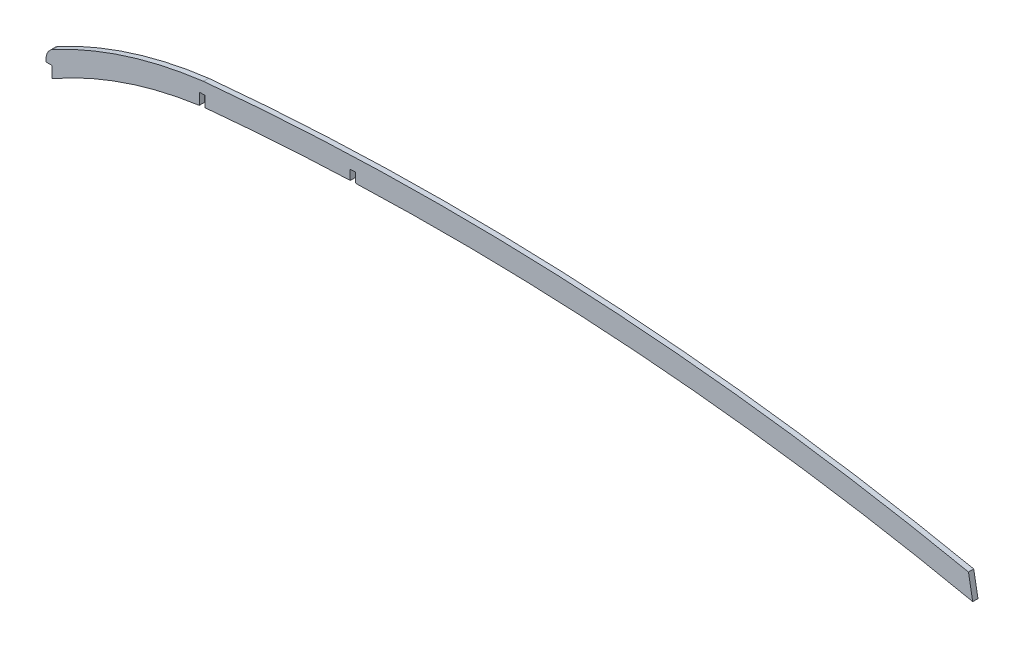
SolidWorks part; units mm, degrees
material "Balsa"
ref_plane "Front Plane" through (0, 0, 0) normal (0, 0, 1) x (1, 0, 0)
ref_plane "Top Plane" through (0, 0, 0) normal (0, 1, 0) x (1, 0, 0)
ref_plane "Right Plane" through (0, 0, 0) normal (1, 0, 0) x (0, 0, -1)
sketch "Sketch1" plane through (0, 0, 0) normal (0, 0, 1) x (1, 0, 0)
  line L0 (0, 101.6) -> (0, 100.0553)
  line L1 (0, -1.7463) -> (0, 1.7463) construction
  line L2 (0, 86.36) -> (8.1082, 86.36) construction
  line L3 (3.7499, 106.3536) -> (3.7499, -82.5359) construction
  line L4 (8.1082, 101.6) -> (0, 101.6) construction
  line L5 (92.329, 130.518) -> (92.329, 123.5672)
  line L6 (3.7499, 93.1973) -> (0, 91.0322) construction
  line L7 (0, 99.5163) -> (0, 88.039) construction
  line L8 (558.2295, 97.6273) -> (555.6382, 111.8229)
  line L9 (0, 91.0322) -> (0, 86.36) construction
  line L10 (3.7499, 93.1973) -> (3.7499, 100.0553)
  line L11 (3.7499, 100.0553) -> (0, 97.8902) construction
  line L12 (0, 97.8902) -> (0, 91.0322) construction
  line L13 (3.7499, 100.0553) -> (0, 100.0553)
  line L14 (0, 100.0553) -> (0, 97.8902) construction
  line L17 (92.3925, 137.6297) -> (92.3925, -54.5591) construction
  line L18 (95.631, 130.518) -> (95.631, 124.0109)
  line L19 (95.5675, -54.5591) -> (95.5675, 137.6297) construction
  line L20 (95.5675, 137.6297) -> (92.3925, 137.6297) construction
  line L21 (93.98, 137.6297) -> (93.98, 130.518) construction
  line L22 (92.329, 130.518) -> (95.631, 130.518)
  line L23 (92.329, 123.5672) -> (92.329, 122.506) construction
  line L24 (95.631, 124.0109) -> (95.631, 123.1918) construction
  line L25 (197.4984, -131.9724) -> (196.7865, -114.9693)
  line L26 (186.671, 126.627) -> (186.2782, 136.0069)
  line L27 (194.3262, -132.1052) -> (193.6143, -115.1021)
  line L28 (183.4987, 126.4942) -> (183.106, 135.8741)
  line L29 (193.6143, -115.1021) -> (196.7865, -114.9693)
  line L30 (186.671, 126.627) -> (183.4987, 126.4942)
  line L31 (194.3262, -132.1052) -> (197.4984, -131.9724)
  line L32 (183.106, 135.8741) -> (186.2782, 136.0069)
  line L33 (183.106, 135.8741) -> (186.2782, 136.0069) construction
  line L35 (186.671, 126.627) -> (183.4987, 126.4942) construction
  line L37 (183.4987, 126.4942) -> (183.106, 135.8741) construction
  line L39 (186.671, 126.627) -> (186.2782, 136.0069) construction
  line L41 (183.106, 135.8741) -> (186.671, 126.627) construction
  line L42 (184.8885, 131.2506) -> (184.9758, 129.1656) construction
  line L43 (183.294, 129.865) -> (183.0502, 135.6897)
  line L44 (186.5939, 129.9858) -> (186.3493, 135.8278)
  line L45 (183.0502, 135.6897) -> (186.3493, 135.8278)
  line L46 (183.2948, 129.8477) -> (183.294, 129.865) construction
  arc A0 (4.3005, 108.7585) -> (94.8544, 137.376) centre (127, -121.92) cw
  arc A1 (4.3005, 108.7585) -> (0, 101.6) centre (8.1082, 101.6) ccw
  arc A2 (3.7499, 93.1973) -> (0, 86.36) centre (8.1082, 86.36) ccw construction
  arc A3 (94.8544, 137.376) -> (555.6382, 111.8229) centre (240.8652, -1397) cw
  arc A4 (3.7499, 93.1973) -> (92.329, 123.5672) centre (127, -121.92) cw
  arc A5 (96.3112, 124.0967) -> (183.294, 129.865) centre (240.8652, -1397) cw
  arc A6 (10.5733, 96.9655) -> (96.3112, 124.0967) centre (127, -121.92) cw construction
  arc A7 (94.4927, 137.3434) -> (3.7499, 106.3536) centre (112.883, -64.8553) ccw construction
  arc A8 (96.3112, 124.0967) -> (552.9103, 98.7469) centre (240.8652, -1397) cw construction
  arc A9 (4.3005, 108.7585) -> (94.8544, 137.376) centre (127, -121.92) cw construction
  arc A10 (92.329, 123.5672) -> (95.631, 124.0109) centre (127, -121.92) cw construction
  arc A11 (94.8544, 137.376) -> (555.6382, 111.8229) centre (240.8652, -1397) cw construction
  arc A12 (95.631, 124.0109) -> (96.3112, 124.0967) centre (127, -121.92) cw
  arc A13 (556.7512, 105.7321) -> (99.1899, 122.2822) centre (270.5046, -1474.7614) ccw construction
  arc A14 (183.294, 129.865) -> (183.3575, 129.8673) centre (240.8652, -1397) cw construction
  arc A15 (184.9439, 129.9263) -> (185.3927, 129.9426) centre (240.8652, -1397) cw construction
  arc A16 (183.3575, 129.8673) -> (184.9439, 129.9263) centre (240.8652, -1397) cw construction
  arc A17 (185.3927, 129.9426) -> (186.5304, 129.9835) centre (240.8652, -1397) cw construction
  arc A18 (186.5939, 129.9858) -> (558.2295, 97.6273) centre (240.8652, -1397) cw
  arc A19 (186.5304, 129.9835) -> (186.5939, 129.9858) centre (240.8652, -1397) cw construction
  spline S0 degree 3 poles (981.3177, 1818.2675) (1139.722, 204.4849) (873.2182, 1.0169) (565.628, -88.9106) (559.2919, -90.7077) (-121.8164, -278.7114) (-929.5333, 36.0269) (-1233.6865, -867.5095) knots -11.664502 -11.664502 -11.664502 -11.664502 0.25 0.25 0.5 0.5 27.071012 27.071012 27.071012 27.071012 only from (590.8643, -81.3536) to (514.7143, -102.4537) construction
  spline S1 degree 3 poles (1062.5522, -1662.3274) (1783.386, 752.2598) (1192.007, 51.9761) (480.6823, -110.4688) (472.1454, -112.3347) (455.0337, -115.879) (446.4591, -117.5582) (433.5613, -119.8984) (429.2558, -120.648) (422.7903, -121.7356) (420.6337, -122.0915) (417.3979, -122.6188) (416.3191, -122.7935) (329.7173, -136.7537) (244.3749, -151.8452) (-150.7518, 1789.6158) knots -20.37019 -20.37019 -20.37019 -20.37019 0.25 0.25 0.5 0.5 0.75 0.75 0.875 0.875 0.9375 0.9375 0.96875 0.96875 3.445896 3.445896 3.445896 3.445896 only from (514.7143, -102.4537) to (412.003, -123.4859) construction
  spline S2 degree 3 poles (-1526.2092, 975.8893) (-966.7298, 244.4948) (-373.5074, -121.9571) (226.7788, -133.168) (266.5142, -132.8729) (279.7628, -132.6016) (299.6408, -131.9345) (306.2677, -131.6688) (319.5231, -131.0505) (326.1536, -130.6977) (943.6584, -93.7895) (1501.3881, 309.0053) (2017.121, 1001.2295) knots -5.168103 -5.168103 -5.168103 -5.168103 0.25 0.5 0.5 0.625 0.625 0.6875 0.6875 0.75 0.75 6.511417 6.511417 6.511417 6.511417 only from (94.4926, -125.8525) to (412.003, -123.4859) construction
  spline S3 degree 3 poles (82.8406, 1879.826) (-241.5287, 509.6599) (-195.4311, -0.6421) (32.0968, -110.0953) (39.5136, -113.1375) (50.922, -117.0433) (54.7721, -118.2354) (60.6197, -119.8556) (62.5829, -120.3681) (66.5243, -121.3341) (68.5001, -121.787) (343.1899, -180.4478) (711.1357, 326.3263) (1193.75, 1513.3939) knots -7.368418 -7.368418 -7.368418 -7.368418 0.25 0.25 0.5 0.5 0.625 0.625 0.6875 0.6875 0.75 0.75 9.354609 9.354609 9.354609 9.354609 only from (3.7499, -94.8626) to (94.4926, -125.8525) construction
  spline S6 degree 3 poles (590.8643, -81.3536) (584.5771, -83.3154) (578.2709, -85.2143) (565.628, -88.9106) (559.2919, -90.7077) (540.2459, -95.9648) (527.5015, -99.2922) (514.7143, -102.4537) knots 0 0 0 0 0.25 0.25 0.5 0.5 1 1 1 1 construction
  spline S7 degree 3 poles (514.7143, -102.4537) (506.2284, -104.5517) (497.724, -106.577) (480.6823, -110.4688) (472.1454, -112.3347) (455.0337, -115.879) (446.4591, -117.5582) (433.5613, -119.8984) (429.2558, -120.648) (422.7903, -121.7356) (420.6337, -122.0915) (417.3979, -122.6188) (416.3191, -122.7935) (414.1613, -123.1413) (413.0825, -123.3155) (412.003, -123.4859) knots 0 0 0 0 0.25 0.25 0.5 0.5 0.75 0.75 0.875 0.875 0.9375 0.9375 0.96875 0.96875 1 1 1 1 construction
  spline S8 degree 3 poles (94.4926, -125.8525) (120.9278, -128.4258) (173.8258, -132.179) (226.7788, -133.168) (266.5142, -132.8729) (279.7628, -132.6016) (299.6408, -131.9345) (306.2677, -131.6688) (319.5231, -131.0505) (326.1536, -130.6977) (359.2877, -128.7173) (385.6949, -126.4433) (412.003, -123.4859) knots 0 0 0 0 0.25 0.5 0.5 0.625 0.625 0.6875 0.6875 0.75 0.75 1 1 1 1 construction
  spline S9 degree 3 poles (3.7499, -94.8626) (10.597, -99.2271) (17.6385, -103.1401) (32.0968, -110.0953) (39.5136, -113.1375) (50.922, -117.0433) (54.7721, -118.2354) (60.6197, -119.8556) (62.5829, -120.3681) (66.5243, -121.3341) (68.5001, -121.787) (78.4043, -123.9021) (86.408, -125.1172) (94.4926, -125.8525) knots 0 0 0 0 0.25 0.25 0.5 0.5 0.625 0.625 0.6875 0.6875 0.75 0.75 1 1 1 1 construction
  spline S15 degree 3 poles (587.4426, -62.5747) (587.1827, -61.1511) (586.6535, -58.2526) (585.7873, -53.5174) (584.8512, -48.394) (583.8406, -42.8532) (582.7565, -36.9006) (581.5991, -30.5376) (580.1295, -22.4773) (578.3524, -12.6853) (576.2505, -1.1976) (574.1192, 10.4518) (571.9272, 22.5233) (569.819, 34.0829) (567.7342, 45.5019) (565.8232, 55.9911) (564.3841, 63.8754) (563.4512, 68.9947) (562.9209, 71.9076) (562.4102, 74.7138) (561.9192, 77.4122) (561.4478, 80.0018) (560.9959, 82.4822) (560.5637, 84.8528) (560.1512, 87.1138) (559.7582, 89.2651) (559.385, 91.3073) (559.0312, 93.2414) (558.6975, 95.0661) (558.3822, 96.7905) (558.1867, 97.8615) (558.0896, 98.3936) knots 0 0 0 0 0.031687 0.064515 0.098497 0.133644 0.169967 0.207478 0.246191 0.30842 0.370332 0.432609 0.495165 0.563925 0.620591 0.686243 0.746551 0.766006 0.785258 0.804303 0.823142 0.841774 0.860197 0.878411 0.896416 0.91421 0.931793 0.949164 0.966322 0.983268 1 1 1 1 construction
  point P53 (93.98, 130.518)
  dimension "D4" = 8.1082
  dimension "D2" = 127
  dimension "D8" = 1397
  dimension "D9" = 30
  dimension "D1" = 15.24
  dimension "D3" = 8.1082
  dimension "D5" = 8.1082
  dimension "D6" = 101.6
  dimension "D7" = 121.92
  dimension "D10" = 6.858
  dimension "D11" = 3.7499
  dimension "D12" = 3.302
  dimension "D13" = 6.858
  dimension "D14" = 3.302
  dimension "D15" = 5.842
extrude "Boss-Extrude1" add sketch "Sketch1" along normal mid plane 3.175
